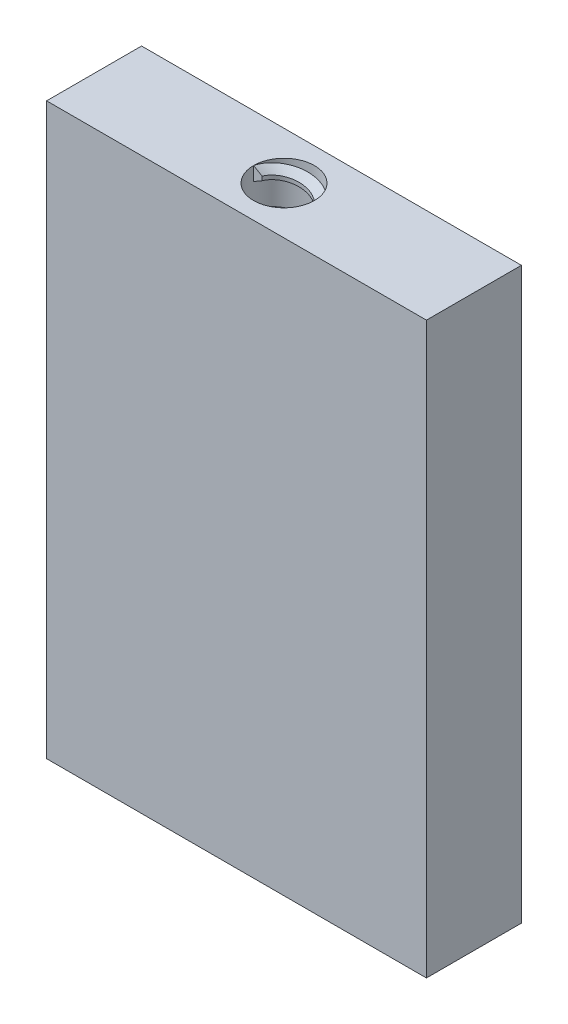
SolidWorks part; units mm, degrees
ref_plane "Front Plane" through (0, 0, 0) normal (0, 0, 1) x (1, 0, 0)
ref_plane "Top Plane" through (0, 0, 0) normal (0, 1, 0) x (1, 0, 0)
ref_plane "Right Plane" through (0, 0, 0) normal (1, 0, 0) x (0, 0, -1)
sketch "Sketch2" plane through (0, 0, 0) normal (0, 0, 1) x (1, 0, 0)
  line L1 (-25.4, -38.1) -> (25.4, -38.1)
  line L2 (-25.4, -38.1) -> (-25.4, 38.1)
  line L3 (-25.4, 38.1) -> (25.4, 38.1)
  line L4 (25.4, -38.1) -> (25.4, 38.1)
  line L5 (-25.4, -38.1) -> (25.4, 38.1) construction
  line L6 (-25.4, 38.1) -> (25.4, -38.1) construction
  point P0 (0, 0)
  dimension "D1" = 76.2
  dimension "D2" = 50.8
extrude "Flip Sign" add sketch "Sketch2" along normal blind 6.35 and the other way blind 6.35 contours L3 L4 L1 L2
sketch "Sketch3" plane through (0, 38.1, 0) normal (0, 1, 0) x (1, 0, 0)
  point P0 (0, 0)
hole_wizard "#95 (0.32) Diameter Hole1" positions "Sketch3" profile "Sketch4" hole size "#95" standard "ANSI Inch"
sketch "Sketch4" plane through (0, 38.1, 0) normal (1, 0, 0) x (0, 0, 1)
  line L0 (0, 0) -> (0, 78.6419)
  line L1 (0, 78.6419) -> (4.064, 76.2)
  line L2 (4.064, 76.2) -> (4.064, 0)
  line L5 (4.064, 0) -> (0, 0)
  line L10 (0, 78.6419) -> (-4.064, 76.2) construction
  line L11 (0, -6.35) -> (0, 107.95) construction
  dimension "Hole Dia." = 8.128
  dimension "Hole Depth" = 76.2
  dimension "Drill Angle" = 118
thread "Thread2" pitch 2.1167 method extrude profile "Thread Profile6" start angle 0, offset 0, length 76.2, pitch 5.08, diameter 8.128
ref_plane "Plane6" through (-4.064, 38.1, 0) normal (0, 0, 1) x (-1, 0, 0)
sketch "Thread Profile6" plane through (-4.064, 38.1, 0) normal (0, 0, 1) x (-1, 0, 0)
  line L0 (0, 0) -> (0, 2.1167) construction
  line L11 (0, 0) -> (0, 1.8521)
  line L12 (0, 1.8521) -> (-1.1457, 1.1906)
  line L13 (-1.1457, 1.1906) -> (-1.1457, 0.6615)
  line L15 (-1.1457, 0.6615) -> (0, 0)
  line L17 (-1.1457, 0.926) -> (0, 0.926) construction
  point P2 (0, 0)
  dimension "Pitch" = 2.1167
  dimension "Profile_Angle" = 60
  dimension "Profile_Land" = 0.5292
  dimension "Profile_Height" = 1.1457
sketch "Sketch22" plane through (0, -38.1, 0) normal (0, -1, 0) x (1, 0, 0)
  line L1 (-25.4, -6.35) -> (25.4, -6.35)
  line L2 (-25.4, -6.35) -> (-25.4, 6.35)
  line L3 (-25.4, 6.35) -> (25.4, 6.35)
  line L4 (25.4, -6.35) -> (25.4, 6.35)
  line L5 (-25.4, -6.35) -> (25.4, 6.35) construction
  line L6 (-25.4, 6.35) -> (25.4, -6.35) construction
  point P0 (0, 0)
extrude "Cut-Extrude1" cut sketch "Sketch22" along normal blind 12.7
